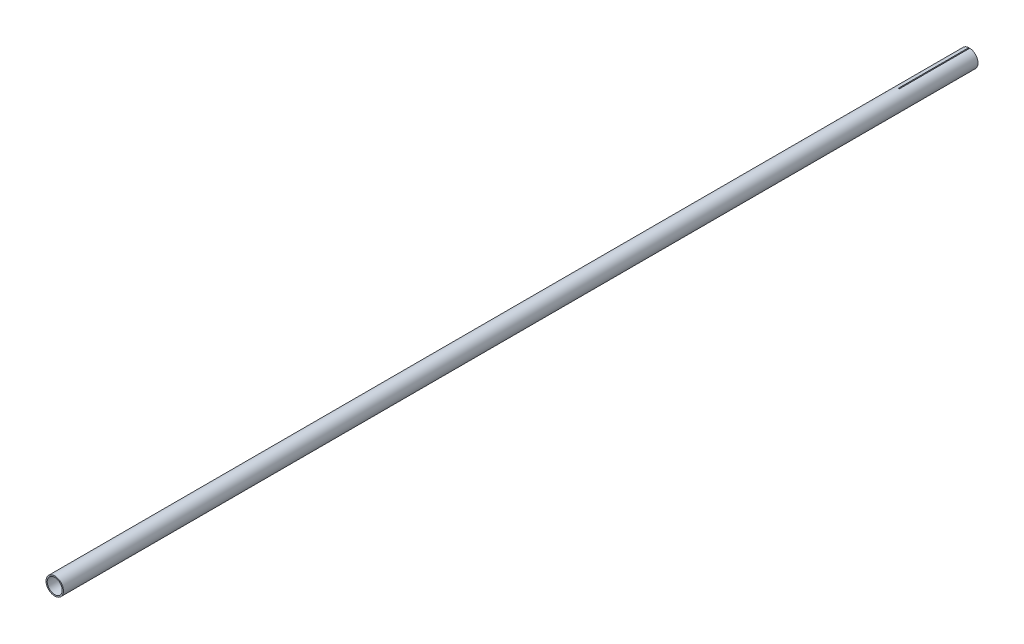
SolidWorks part; units mm, degrees
ref_plane "Front Plane" through (0, 0, 0) normal (0, 0, 1) x (1, 0, 0)
ref_plane "Top Plane" through (0, 0, 0) normal (0, 1, 0) x (1, 0, 0)
ref_plane "Right Plane" through (0, 0, 0) normal (1, 0, 0) x (0, 0, -1)
sketch "Sketch1" plane through (0, 0, 0) normal (0, 0, 1) x (1, 0, 0)
  circle A0 centre (0, 0) radius 17.46
  circle A1 centre (0, 0) radius 15
  dimension "D1" = 34.92
  dimension "D2" = 30
extrude "Boss-Extrude1" add sketch "Sketch1" along normal blind 1828.8
sketch "Sketch2" plane through (0, 0, 0) normal (0, 1, 0) x (1, 0, 0)
  line L0 (0, 0) -> (0, -15) construction
  line L1 (0, -19) -> (0, -31) construction
  circle A0 centre (0, -15) radius 4
  circle A1 centre (0, -31) radius 4
  dimension "D2" = 8
  dimension "D4" = 8
  dimension "D1" = 15
  dimension "D3" = 12
sketch "Sketch4" plane through (0, 0, 0) normal (0, 0, 1) x (1, 0, 0)
  line L0 (0, 17.46) -> (0, -17.46) construction
  line L1 (2.54, 15) -> (-2.54, 15) construction
  line L2 (0, 0) -> (5.9684, 0) construction
  line L3 (2.54, -15) -> (-2.54, -15) construction
  line L5 (1.04, -25) -> (-1.04, -25)
  line L6 (1.04, -25) -> (1.04, 25)
  line L7 (1.04, 25) -> (-1.04, 25)
  line L8 (-1.04, -25) -> (-1.04, 25)
  line L9 (1.04, -25) -> (-1.04, 25) construction
  line L10 (1.04, 25) -> (-1.04, -25) construction
  circle A0 centre (0, 0) radius 17.46 construction
  circle A1 centre (0, 0) radius 15 construction
  point P10 (0, 15)
  dimension "D1" = 2.54
  dimension "D2" = 50
  dimension "D3" = 2.08
extrude "Cut-Extrude2" cut sketch "Sketch4" along normal blind 141
sketch "Sketch5" plane through (0, 0, 0) normal (0, 1, 0) x (1, 0, 0)
  line L0 (0, 69.4642) -> (0, 24.2519) construction
ref_axis "Axis1" through (0, 0, -69.4642) along (0, 0, 1)
